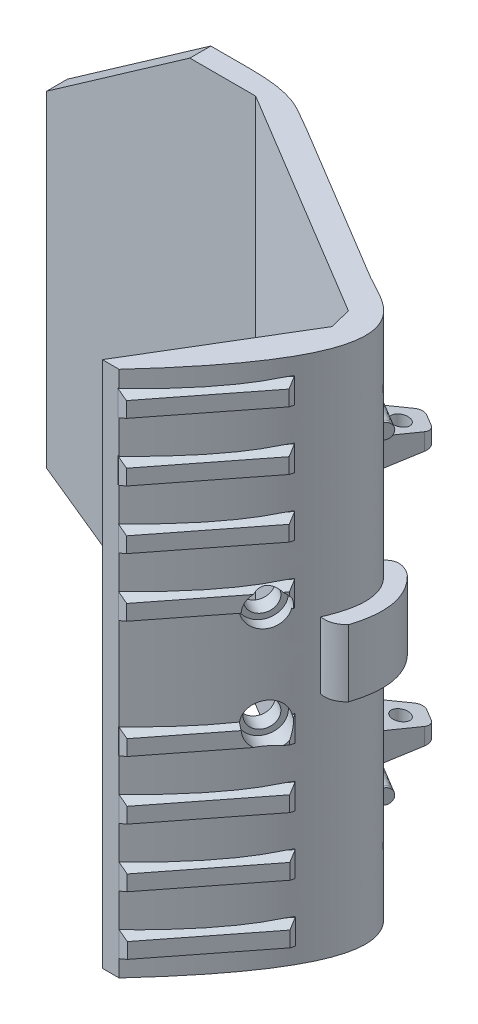
SolidWorks part; units mm, degrees
ref_plane "前视基准面" through (0, 0, 0) normal (0, 0, 1) x (1, 0, 0)
ref_plane "上视基准面" through (0, 0, 0) normal (0, 1, 0) x (1, 0, 0)
ref_plane "右视基准面" through (0, 0, 0) normal (1, 0, 0) x (0, 0, -1)
sketch "草图1" plane through (0, 0, 0) normal (0, 1, 0) x (1, 0, 0)
  line L5 (43.7362, -7.8141) -> (33.4354, -24.9575)
  line L6 (33.4354, -24.9575) -> (35.4354, -24.9575)
  line L7 (43.0861, -5.207) -> (15.3139, 11.4803)
  line L8 (12.0784, 13.9803) -> (10.0784, 13.9803)
  line L9 (40.9632, -0.4315) -> (21.9611, 10.9861)
  line L10 (10.0784, 13.9803) -> (-9.6861, 13.9803)
  line L11 (-9.6861, 11.4803) -> (15.3139, 11.4803)
  line L12 (-9.6861, 13.9803) -> (-9.6861, 11.4803)
  line L13 (43.7362, -7.8141) -> (43.0861, -5.207)
  line L14 (85.0447, -26.9183) -> (-3.1183, 26.0554) construction
  spline S0 degree 3 poles (12.0784, 13.9803) (18.0822, 13.9803) (19.1386, 12.5006) (21.9611, 10.9861) knots 0 0 0 0 0.428174 0.428174 0.428174 0.428174
  spline S1 degree 3 poles (40.9632, -0.4315) (44.691, -2.6714) (54.1274, -4.5601) (35.4354, -24.9575) knots 0.746299 0.746299 0.746299 0.746299 1 1 1 1
  point P3 (44.7148, -6.1855)
  dimension "D3" = 90
  dimension "D2" = 149
  dimension "D6" = 20
  dimension "D7" = 180
  dimension "D11" = 83
  dimension "D1" = 2
  dimension "D4" = 2
  dimension "D5" = 34.3
  dimension "D8" = 2.5
  dimension "D9" = 25
  dimension "D10" = 3
extrude "凸台-拉伸1" add sketch "草图1" along normal blind 63
sketch "草图2" plane through (10.6756, 0, -17.7672) normal (0.515, 0, -0.8572) x (-0.8572, 0, -0.515)
  line L0 (-13.1661, 31.5) -> (-35.3345, 31.5) construction
  line L1 (-13.1661, 63) -> (-13.1661, 0) construction
  line L2 (-35.3345, 63) -> (-35.3345, 0) construction
  line L4 (-32.3345, 24.5) -> (-18.3345, 24.5)
  line L5 (-32.3345, 24.5) -> (-32.3345, 38.5)
  line L6 (-32.3345, 38.5) -> (-18.3345, 38.5)
  line L7 (-18.3345, 24.5) -> (-18.3345, 38.5)
  line L8 (-32.3345, 24.5) -> (-18.3345, 38.5) construction
  line L9 (-32.3345, 38.5) -> (-18.3345, 24.5) construction
  point P6 (-25.3345, 31.5)
  dimension "D1" = 14
  dimension "D2" = 14
  dimension "D3" = 3
extrude "凸台-拉伸2" add sketch "草图2" along normal blind 1 draft 25
sketch "草图6" plane through (0, 0, 0) normal (0, -1, 0) x (1, 0, 0)
  line L0 (13.0784, -13.9655) -> (24.6266, -11.9292)
  line L1 (15.3139, -11.4803) -> (43.0861, 5.207) construction
  spline S0 degree 3 poles (21.9611, -10.9861) (19.1386, -12.5006) (18.0822, -13.9803) (12.0784, -13.9803) knots 0 0 0 0 0.428174 0.428174 0.428174 0.428174 construction
  dimension "D1" = 21
  dimension "D2" = 1
ref_plane "基准面2" through (2.7826, 0, -15.7809) normal (0.1736, 0, -0.9848) x (0.9848, 0, 0.1736)
sketch "草图7" plane through (2.7826, 0, -15.7809) normal (0.1736, 0, -0.9848) x (0.9848, 0, 0.1736)
  line L1 (11.4673, -18.5) -> (22.4673, -18.5)
  line L2 (11.4673, -18.5) -> (11.4673, -44.5)
  line L3 (11.4673, -44.5) -> (22.4673, -44.5)
  line L4 (22.4673, -18.5) -> (22.4673, -44.5)
  line L5 (9.4673, -63) -> (9.4673, 0) construction
  line L7 (37.6151, -24.5) -> (24.5449, -24.5) construction
  line L8 (24.5449, -38.5) -> (37.6151, -38.5) construction
  dimension "D1" = 6
  dimension "D2" = 6
  dimension "D3" = 11
  dimension "D4" = 2
sketch "草图3" plane through (11.1906, 0, -18.6243) normal (0.515, 0, -0.8572) x (-0.8572, 0, -0.515)
  line L0 (-18.8008, 31.5) -> (-31.8682, 31.5) construction
  line L1 (-18.8008, 24.9663) -> (-18.8008, 38.0337) construction
  line L2 (-31.8682, 38.0337) -> (-31.8682, 24.9663) construction
  line L3 (-25.3345, 38.0337) -> (-25.3345, 24.9663) construction
  line L4 (-18.8008, 38.0337) -> (-31.8682, 38.0337) construction
  line L5 (-31.8682, 24.9663) -> (-18.8008, 24.9663) construction
  line L6 (-22.1526, 34.682) -> (-28.5165, 28.318) construction
  line L7 (-21.0919, 33.6213) -> (-27.4559, 27.2574)
  line L8 (-23.2132, 35.7426) -> (-29.5772, 29.3787)
  line L9 (-22.1526, 28.318) -> (-28.5165, 34.682) construction
  line L10 (-23.2132, 27.2574) -> (-29.5772, 33.6213)
  line L11 (-21.0919, 29.3787) -> (-27.4559, 35.7426)
  arc A0 (-21.0919, 33.6213) -> (-23.2132, 35.7426) centre (-22.1526, 34.682) ccw
  arc A1 (-29.5772, 29.3787) -> (-27.4559, 27.2574) centre (-28.5165, 28.318) ccw
  arc A2 (-23.2132, 27.2574) -> (-21.0919, 29.3787) centre (-22.1526, 28.318) ccw
  arc A3 (-27.4559, 35.7426) -> (-29.5772, 33.6213) centre (-28.5165, 34.682) ccw
  point P14 (-25.3345, 31.5)
  point P19 (-25.3345, 31.5)
  dimension "D1" = 3
  dimension "D2" = 3
  dimension "D3" = 9
  dimension "D4" = 9
extrude "切除-拉伸1" cut sketch "草图3" against normal blind 0.6 contours L7 A0 L8 L11 | L7 L11 L8 L10 | L10 A2 L11 L7 | L8 A1 L7 L10 | L11 A3 L10 L8 region at (30.7231, 34.0473, -6.8881) region at (30.7231, 28.9527, -6.8881) region at (32.9066, 31.5, -5.5761) region at (35.0901, 28.9527, -4.2641) region at (35.0901, 34.0473, -4.2641)
ref_plane "基准面1" through (10.1606, 0, -16.91) normal (-0.515, 0, 0.8572) x (0.8572, 0, 0.515)
extrude "凸台-拉伸4" add sketch "草图7" along normal blind 2 draft 35 and the other way blind 2
sketch "草图4" plane through (9.1305, 0, -15.1957) normal (-0.515, 0, 0.8572) x (0.8572, 0, 0.515)
  line L0 (41.5138, 31.5) -> (-14.9499, 31.5) construction
  line L1 (41.5138, 63) -> (41.5138, 0) construction
  line L2 (3.1528, 63) -> (3.1528, 0) construction
  circle A0 centre (9.6528, 25.5) radius 1.65
  circle A1 centre (9.6528, 37.5) radius 1.65
  dimension "D1" = 3.3
  dimension "D2" = 12
  dimension "D3" = 6.5
extrude "切除-拉伸2" cut sketch "草图4" against normal through all
sketch "草图5" plane through (10.1606, 0, -16.91) normal (-0.515, 0, 0.8572) x (0.8572, 0, 0.515)
  circle A0 centre (9.6528, 25.5) radius 2.3
  circle A1 centre (9.6528, 37.5) radius 2.3
  dimension "D1" = 4.6
extrude "切除-拉伸3" cut sketch "草图5" against normal through all
ref_plane "基准面3" through (2.7826, 0, -15.7809) normal (-0.1736, 0, 0.9848) x (0.9848, 0, 0.1736)
sketch "草图9" plane through (0, 0, 0) normal (0, -1, 0) x (1, 0, 0)
  line L0 (35.4354, 24.9575) -> (56.6549, -2.2022) construction
  line L4 (43.7362, 7.8141) -> (33.4354, 24.9575) construction
  point P5 (54.4848, -3.8476)
  dimension "D1" = 7
ref_plane "基准面4" through (34.1121, 0, 26.6513) normal (-0.788, 0, -0.6157) x (-0.6157, 0, 0.788)
sketch "草图10" plane through (34.1121, 0, 26.6513) normal (-0.788, 0, -0.6157) x (-0.6157, 0, 0.788)
  line L0 (-17.078, 51) -> (-2.078, 51)
  line L1 (-2.1495, 63) -> (-2.1495, 0) construction
  line L2 (-17.1495, 5) -> (-2.1495, 5)
  line L3 (-17.1495, 5) -> (-17.1495, 2)
  line L4 (-17.1495, 2) -> (-2.1495, 2)
  line L5 (-2.1495, 5) -> (-2.1495, 2)
  line L6 (-17.1392, 9) -> (-2.1392, 9)
  line L11 (-17.1392, 12) -> (-2.1392, 12)
  line L12 (-17.1392, 12) -> (-17.1392, 9)
  line L13 (-2.1392, 12) -> (-2.1392, 9)
  line L14 (-17.078, 54) -> (-2.078, 54)
  line L15 (-17.129, 16) -> (-2.129, 16)
  line L16 (-17.129, 19) -> (-2.129, 19)
  line L17 (-17.129, 19) -> (-17.129, 16)
  line L18 (-2.129, 19) -> (-2.129, 16)
  line L19 (-17.078, 54) -> (-17.078, 51)
  line L20 (-17.1188, 23) -> (-2.1188, 23)
  line L21 (-17.1188, 26) -> (-2.1188, 26)
  line L22 (-17.1188, 26) -> (-17.1188, 23)
  line L23 (-2.1188, 26) -> (-2.1188, 23)
  line L24 (-2.078, 54) -> (-2.078, 51)
  line L25 (-17.1086, 30) -> (-2.1086, 30)
  line L26 (-17.1086, 33) -> (-2.1086, 33)
  line L27 (-17.1086, 33) -> (-17.1086, 30)
  line L28 (-2.1086, 33) -> (-2.1086, 30)
  line L29 (-17.0678, 58) -> (-2.0678, 58)
  line L30 (-17.0984, 37) -> (-2.0984, 37)
  line L31 (-17.0984, 40) -> (-2.0984, 40)
  line L32 (-17.0984, 40) -> (-17.0984, 37)
  line L33 (-2.0984, 40) -> (-2.0984, 37)
  line L34 (-17.0678, 61) -> (-2.0678, 61)
  line L35 (-17.0882, 44) -> (-2.0882, 44)
  line L36 (-17.0882, 47) -> (-2.0882, 47)
  line L37 (-17.0882, 47) -> (-17.0882, 44)
  line L38 (-2.0882, 47) -> (-2.0882, 44)
  line L39 (-17.0678, 61) -> (-17.0678, 58)
  line L44 (-2.0678, 61) -> (-2.0678, 58)
  line L52 (-2.1495, 31.5) -> (-17.1086, 31.5) construction
  point P22 (0, 0)
  dimension "D1" = 3
  dimension "D2" = 9
  dimension "D3" = 15
extrude "凸台-拉伸6" add sketch "草图10" against normal blind 1 draft 30 and the other way blind 1 contours L5 L2 L3 L4 | L13 L11 L12 L6 | L23 L21 L22 L20 | L38 L36 L37 L35 | L16 L18 L15 L17 | L31 L33 L30 L32 | L0 L24 L14 L19 | L29 L44 L34 L39 region at (40.0529, 3.5, 19.0474) region at (40.0466, 10.5, 19.0555) region at (40.034, 24.5, 19.0715) region at (40.0152, 45.5, 19.0957)
sketch "草图12" plane through (35.5843, 0, 21.3812) normal (-0.8572, 0, -0.515) x (-0.515, 0, 0.8572)
  line L0 (4.1722, 31.5) -> (-9.4999, 31.5) construction
  line L1 (4.1722, 63) -> (4.1722, 0) construction
  line L2 (-17.7278, 63) -> (-17.7278, 0) construction
  circle A0 centre (-9.2278, 25.5) radius 1.65
  circle A1 centre (-9.2278, 37.5) radius 1.65
  dimension "D1" = 3.3
  dimension "D2" = 12
  dimension "D3" = 8.5
extrude "切除-拉伸4" cut sketch "草图12" against normal blind 2
sketch "草图13" plane through (37.2986, 0, 22.4113) normal (-0.8572, 0, -0.515) x (-0.515, 0, 0.8572)
  circle A0 centre (-9.2278, 25.5) radius 2.3
  circle A1 centre (-9.2278, 37.5) radius 2.3
  dimension "D1" = 4.6
extrude "切除-拉伸5" cut sketch "草图13" against normal through all
chamfer "倒角1" distance 12 angle 55 2 edges at (-9.6861, 63, -12.7303) (-9.6861, 0, -12.7303) first distance on face at (-9.6861, 31.5, -12.7303)
sketch "草图14" plane through (10.6756, 0, -17.7672) normal (0.515, 0, -0.8572) x (-0.8572, 0, -0.515)
  line L0 (-35.3345, 31.5) -> (5.0388, 31.5) construction
  line L1 (-35.3345, 63) -> (-35.3345, 0) construction
  line L2 (-35.3345, 63) -> (-13.1661, 63) construction
  line L3 (-28.1661, 54) -> (-18.1661, 54)
  line L4 (-28.1661, 54) -> (-28.1661, 59)
  line L5 (-28.1661, 59) -> (-18.1661, 59)
  line L6 (-18.1661, 54) -> (-18.1661, 59)
  line L7 (-13.1661, 63) -> (-13.1661, 44.5) construction
  line L8 (-28.1661, 9) -> (-28.1661, 4)
  line L9 (-28.1661, 4) -> (-18.1661, 4)
  line L10 (-18.1661, 9) -> (-18.1661, 4)
  line L11 (-28.1661, 9) -> (-18.1661, 9)
  dimension "D1" = 5
  dimension "D2" = 10
  dimension "D3" = 4
  dimension "D4" = 5
extrude "凸台-拉伸8" add sketch "草图14" along normal blind 1 draft 25
sketch "草图15" plane through (10.6756, 0, -17.7672) normal (0.515, 0, -0.8572) x (-0.8572, 0, -0.515)
  line L0 (-35.3345, 31.5) -> (9.9606, 31.5) construction
  line L1 (-21.1661, 45) -> (-16.1661, 45)
  line L2 (-21.1661, 45) -> (-21.1661, 48.5)
  line L3 (-21.1661, 48.5) -> (-16.1661, 48.5)
  line L4 (-16.1661, 45) -> (-16.1661, 48.5)
  line L5 (-35.3345, 63) -> (-35.3345, 0) construction
  line L6 (-13.1661, 63) -> (-13.1661, 44.5) construction
  line L7 (-27.1661, 63) -> (-27.1661, -8.1652) construction
  line L9 (-16.1661, 18) -> (-16.1661, 14.5)
  line L10 (-21.1661, 18) -> (-16.1661, 18)
  line L11 (-21.1661, 18) -> (-21.1661, 14.5)
  line L12 (-21.1661, 14.5) -> (-16.1661, 14.5)
  line L13 (-38.1661, 45) -> (-38.1661, 48.5)
  line L14 (-33.1661, 45) -> (-33.1661, 48.5)
  line L15 (-33.1661, 18) -> (-33.1661, 14.5)
  line L16 (-33.1661, 14.5) -> (-38.1661, 14.5)
  line L17 (-38.1661, 18) -> (-38.1661, 14.5)
  line L18 (-33.1661, 18) -> (-38.1661, 18)
  line L19 (-33.1661, 48.5) -> (-38.1661, 48.5)
  line L20 (-33.1661, 45) -> (-38.1661, 45)
  line L21 (-35.3345, 63) -> (-13.1661, 63) construction
  dimension "D1" = 5
  dimension "D2" = 3.5
  dimension "D3" = 3
  dimension "D4" = 14
  dimension "D5" = 14.5
extrude "凸台-拉伸9" add sketch "草图15" along normal blind 5 draft 10 and the other way blind 2
fillet "圆角1" radius 1 8 edges at (27.8635, 46.75, -13.2728) (30.6379, 46.75, -11.6058) (42.4354, 46.75, -4.5171) (45.2098, 46.75, -2.8501) (45.2098, 16.25, -2.8501) (42.4354, 16.25, -4.5171) (30.6379, 16.25, -11.6058) (27.8635, 16.25, -13.2728)
sketch "草图16" plane through (0, 0, 0) normal (0, 1, 0) x (1, 0, 0)
  line L0 (29.2507, 12.4393) -> (26.234, 6.8746) construction
  line L1 (28.5828, 12.8406) -> (29.9187, 12.0379) construction
  line L2 (43.8226, 3.6836) -> (40.6074, -2.1444) construction
  line L3 (43.1546, 4.085) -> (44.4905, 3.2823) construction
  circle A0 centre (28.0592, 10.2415) radius 1
  circle A1 centre (42.615, 1.4946) radius 1
  dimension "D1" = 2
  dimension "D2" = 2
  dimension "D3" = 2.5
  dimension "D4" = 2.5
extrude "切除-拉伸6" cut sketch "草图16" along normal through all
sketch "草图17" plane through (10.6756, 0, -17.7672) normal (0.515, 0, -0.8572) x (-0.8572, 0, -0.515)
  line L0 (-35.3345, 31.5) -> (6.1291, 31.5) construction
  line L1 (-27.1661, 13.5) -> (-40.1661, 13.5)
  line L2 (-27.1661, 13.5) -> (-27.1661, 11.7)
  line L3 (-27.1661, 11.7) -> (-40.1661, 11.7)
  line L4 (-40.1661, 13.5) -> (-40.1661, 11.7)
  line L5 (-35.3345, 45) -> (-35.3345, 18) construction
  line L6 (-40.1661, 49.5) -> (-40.1661, 51.3)
  line L7 (-27.1661, 49.5) -> (-40.1661, 49.5)
  line L8 (-27.1661, 49.5) -> (-27.1661, 51.3)
  line L9 (-27.1661, 51.3) -> (-40.1661, 51.3)
  line L10 (-33.1661, 14.5) -> (-33.1661, 18) construction
  dimension "D1" = 1.8
  dimension "D2" = 1
  dimension "D3" = 13
  dimension "D4" = 6
extrude "凸台-拉伸11" add sketch "草图17" along normal blind 0.9 and the other way blind 2
fillet "圆角2" radius 0.9 4 edges at (39.9966, 13.5, -1.1993) (39.9966, 11.7, -1.1993) (39.9966, 51.3, -1.1993) (39.9966, 49.5, -1.1993)
ref_plane "基准面5" through (0, 31.5, 0) normal (0, 1, 0) x (1, 0, 0)
sketch "草图18" plane through (0, 31.5, 0) normal (0, 1, 0) x (1, 0, 0)
  spline S1 degree 3 poles (-791.1473, -587.7657) (949.4076, 513.9014) (-880.8348, -475.6959) (927.6655, 461.8887) knots 0.206696 0.206696 0.206696 0.206696 1.721982 1.721982 1.721982 1.721982 only from (35.4354, -24.9575) to (40.9632, -0.4315) construction
  spline S2 degree 3 poles (-1602.5699, -1171.4105) (-238.5666, -250.9925) (5.4758, -68.5237) (44.3557, -17.2789) (45.5601, -15.4461) (47.3669, -12.1443) (47.9715, -10.6741) (48.4924, -8.6453) (48.601, -7.9982) (48.6895, -6.7551) (48.669, -6.1587) (48.5014, -5.0266) (48.354, -4.4914) (47.954, -3.5042) (47.7019, -3.053) (47.1333, -2.2435) (46.8175, -1.885) (46.1597, -1.2485) (45.8178, -0.9701) (44.7915, -0.2251) (44.1064, 0.1542) (43.1933, 0.6371) (42.9079, 0.7833) (30.0799, 7.5398) (91.1667, -13.6243) (1983.8038, -477.2261) knots -2.845697 -2.845697 -2.845697 -2.845697 0.125 0.125 0.25 0.25 0.375 0.375 0.4375 0.4375 0.5 0.5 0.5625 0.5625 0.625 0.625 0.6875 0.6875 0.75 0.75 0.875 0.875 0.9375 0.9375 4.018403 4.018403 4.018403 4.018403 only from (36.9099, -26.3087) to (41.9933, 1.2829)
  spline S3 degree 3 poles (48.0739, -10.1642) (48.1664, -9.8781) (48.248, -9.5974) (48.4924, -8.6453) (48.601, -7.9982) (48.6895, -6.7551) (48.669, -6.1587) (48.5014, -5.0266) (48.354, -4.4914) (47.954, -3.5042) (47.7019, -3.053) (47.1341, -2.2447) (46.8193, -1.887) (46.4914, -1.5694) knots 0.349509 0.349509 0.349509 0.349509 0.375 0.375 0.4375 0.4375 0.5 0.5 0.5625 0.5625 0.625 0.625 0.687326 0.687326 0.687326 0.687326
  spline S4 degree 3 poles (45.6025, -11.0303) (48.0987, -5.3355) (45.7438, -3.111) (43.3045, -1.6999) knots 0.822854 0.822854 0.822854 0.822854 0.954861 0.954861 0.954861 0.954861
  spline S5 degree 2 poles (48.0739, -10.1642) (47.0268, -11.2744) (45.6025, -11.0303) knots 0 0 0 1 1 1
  spline S6 degree 3 poles (46.4914, -1.5694) (44.7171, -0.1284) (43.6293, -1.0822) (43.3045, -1.6999) knots 0 0 0 0 1 1 1 1
  point P9 (47.1574, -14.6088)
  point P11 (46.6185, -1.5091)
  point P12 (44.9661, -1.112)
  point P13 (48.1346, -12.1888)
  point P14 (47.078, -13.265)
  point P15 (42.739, -1.355)
  point P16 (44.0033, -0.6456)
  point P17 (42.7021, -1.3363)
  point P18 (43.4466, -0.3587)
  point P19 (45.9521, -11.8357)
  point P20 (0, 0)
  point P21 (48.4747, -10.2373)
  point P22 (47.299, -11.7964)
  point P23 (46.1012, -11.3656)
  point P24 (47.5583, -11.3209)
  point P25 (46.6262, -11.0212)
  point P26 (43.1731, -1.7182)
  point P27 (43.9188, -1.0472)
  point P28 (45.1205, -10.819)
  point P29 (43.2609, -1.7753)
  dimension "D1" = 2
extrude "凸台-拉伸12" add sketch "草图18" along normal blind 4 and the other way blind 4
sketch "草图19" plane through (0, 0, -13.9803) normal (0, 0, -1) x (-1, 0, 0)
  line L0 (-12.0784, 31.5) -> (21.1094, 31.5) construction
  line L1 (-12.0784, 63) -> (-12.0784, 0) construction
  line L2 (-17.4387, 54.5) -> (-17.4387, 50.5)
  line L3 (-17.4387, 8.5) -> (-5.4387, 8.5)
  line L4 (-17.4387, 8.5) -> (-17.4387, 12.5)
  line L5 (-17.4387, 12.5) -> (-5.4387, 12.5)
  line L6 (-5.4387, 8.5) -> (-5.4387, 12.5)
  line L7 (-17.4387, 54.5) -> (-5.4387, 54.5)
  line L8 (-5.4387, 54.5) -> (-5.4387, 50.5)
  line L9 (-17.4387, 50.5) -> (-5.4387, 50.5)
  dimension "D1" = 4
  dimension "D2" = 12
  dimension "D3" = 19
extrude "凸台-拉伸13" add sketch "草图19" along normal blind 1.5 draft 10 and the other way blind 2 draft 10
equation "\"M3_1\"= 3.3"
equation "\"D1@草图12\"=\"M3_1\""
equation "\"D1@草图4\"=\"M3_1\""
